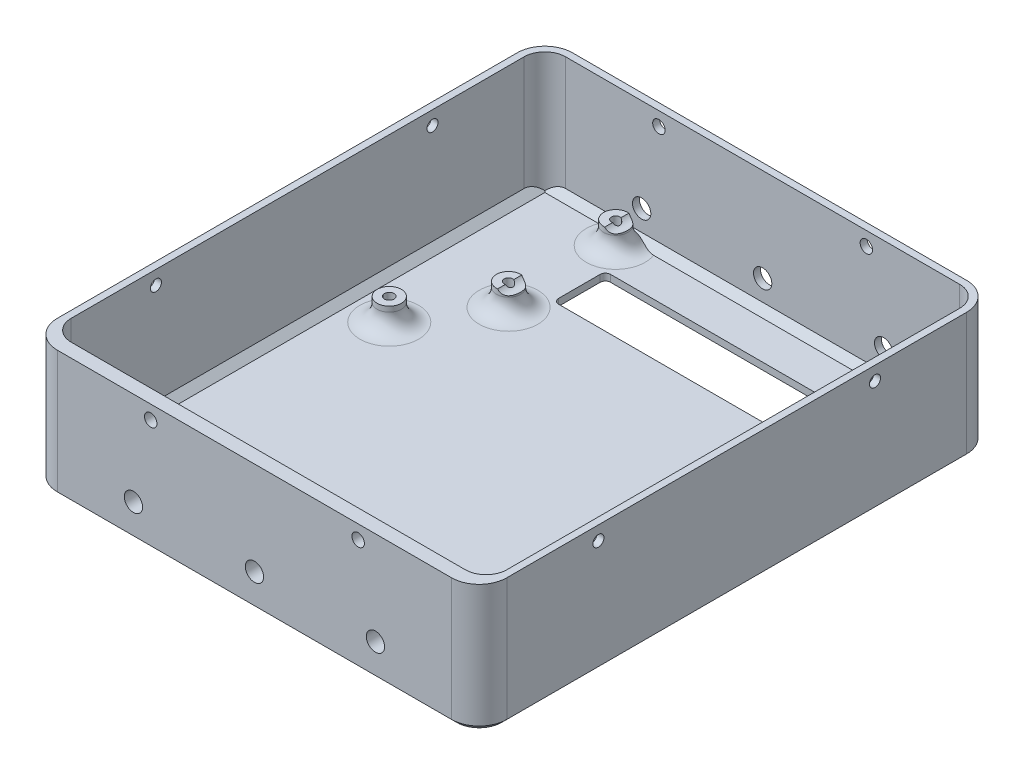
SolidWorks part; units mm, degrees
ref_plane "Front Plane" through (0, 0, 0) normal (0, 0, 1) x (1, 0, 0)
ref_plane "Top Plane" through (0, 0, 0) normal (0, 1, 0) x (1, 0, 0)
ref_plane "Right Plane" through (0, 0, 0) normal (1, 0, 0) x (0, 0, -1)
sketch "Sketch1" plane through (0, 0, 0) normal (0, 1, 0) x (1, 0, 0)
  line L0 (-65, 52) -> (65, 52) construction
  line L1 (-55, -42) -> (55, -42) construction
  line L2 (-55, -42) -> (-55, 42) construction
  line L3 (-55, 42) -> (55, 42) construction
  line L4 (55, -42) -> (55, 42) construction
  line L5 (-55, -42) -> (55, 42) construction
  line L6 (-55, 42) -> (55, -42) construction
  line L7 (51, -38) -> (-51, -38) construction
  line L8 (51, -38) -> (51, 38) construction
  line L9 (51, 38) -> (-51, 38) construction
  line L10 (-51, -38) -> (-51, 38) construction
  line L11 (51, -38) -> (-51, 38) construction
  line L12 (51, 38) -> (-51, -38) construction
  line L13 (65, -52) -> (65, 52)
  line L14 (-65, -52) -> (65, -52)
  line L15 (-65, -52) -> (-65, 52)
  line L16 (-65, 52) -> (-65, 97)
  line L17 (-65, 97) -> (65, 97)
  line L18 (65, 97) -> (65, 52)
  line L19 (0, 52) -> (0, 97) construction
  line L21 (-32.5, 82) -> (32.5, 82)
  line L22 (-32.5, 82) -> (-32.5, 67)
  line L23 (-32.5, 67) -> (32.5, 67)
  line L24 (32.5, 82) -> (32.5, 67)
  line L25 (-32.5, 82) -> (32.5, 67) construction
  line L26 (-32.5, 67) -> (32.5, 82) construction
  line L27 (-37.5, 59) -> (37.5, 59) construction
  line L28 (-37.5, 59) -> (-37.5, 90) construction
  line L29 (-37.5, 90) -> (37.5, 90) construction
  line L30 (37.5, 59) -> (37.5, 90) construction
  line L31 (-37.5, 59) -> (37.5, 90) construction
  line L32 (-37.5, 90) -> (37.5, 59) construction
  circle A0 centre (-51, 38) radius 1.4
  circle A1 centre (51, 38) radius 1.4
  circle A2 centre (51, -38) radius 1.4
  circle A3 centre (-51, -38) radius 1.4
  circle A4 centre (-37.5, 90) radius 1.25
  circle A5 centre (37.5, 90) radius 1.25
  circle A6 centre (37.5, 59) radius 1.25
  circle A7 centre (-37.5, 59) radius 1.25
  point P0 (0, 0)
  point P5 (0, 0)
  point P23 (0, 74.5)
  point P28 (0, 74.5)
  dimension "D1" = 110
  dimension "D5" = 2.8
  dimension "D6" = 2.8
  dimension "D7" = 2.8
  dimension "D8" = 2.8
  dimension "D17" = 2.5
  dimension "D2" = 84
  dimension "D3" = 102
  dimension "D4" = 76
  dimension "D10" = 45
  dimension "D11" = 90
  dimension "D12" = 90
  dimension "D13" = 65
  dimension "D14" = 15
  dimension "D15" = 75
  dimension "D16" = 31
  dimension "D9" = 10
extrude "Boss-Extrude1" add sketch "Sketch1" along normal blind 2
sketch "Sketch2" plane through (0, 2, 0) normal (0, 1, 0) x (1, 0, 0)
  line L0 (-63, 95) -> (-63, -48)
  line L1 (-65, 97) -> (65, 97)
  line L2 (-65, 97) -> (-65, -52)
  line L3 (-65, -52) -> (65, -52)
  line L4 (65, 97) -> (65, -52)
  line L6 (63, 95) -> (63, -48)
  line L7 (-63, 95) -> (63, 95)
  line L8 (-63, 95) -> (-63, -50) construction
  line L11 (-63, -48) -> (63, -48)
  line L13 (-63, -50) -> (63, -50) construction
  line L14 (63, 95) -> (63, -50) construction
  dimension "D1" = 2
  dimension "D2" = 4
extrude "Boss-Extrude2" add sketch "Sketch2" along normal blind 35
sketch "Sketch3" plane through (0, 2, 0) normal (0, 1, 0) x (1, 0, 0)
  circle A0 centre (-51, 38) radius 3.5
  circle A1 centre (-51, 38) radius 1.4
  circle A2 centre (51, 38) radius 1.4
  circle A3 centre (51, 38) radius 3.5
  circle A4 centre (51, -38) radius 1.4764
  circle A5 centre (51, -38) radius 3.5
  circle A6 centre (-51, -38) radius 1.4
  circle A7 centre (-51, -38) radius 3.5
  circle A8 centre (-37.5, 90) radius 1.25
  circle A9 centre (-37.5, 90) radius 3.5
  circle A10 centre (37.5, 90) radius 1.4
  circle A11 centre (37.5, 90) radius 3.5
  circle A12 centre (37.5, 59) radius 1.75
  circle A13 centre (37.5, 59) radius 3.5
  circle A14 centre (-37.5, 59) radius 1.25
  circle A15 centre (-37.5, 59) radius 3.5
  dimension "D1" = 7
  dimension "D2" = 7
  dimension "D3" = 7
  dimension "D4" = 7
extrude "Boss-Extrude3" add sketch "Sketch3" along normal blind 6.5
chamfer "Chamfer1" distance 2 angle 45 4 edges at (63, 2, -23.5) (0, 2, 48) (-63, 2, -23.5) (0, 2, -95)
fillet "Fillet1" radius 5 8 edges at (-51, 2, 34.5) (-51, 2, -41.5) (51, 2, 34.5) (51, 2, -41.5) (-37.5, 2, -62.5) (-37.5, 2, -86.5) (37.5, 2, -62.5) (37.5, 2, -86.5)
fillet "Fillet2" radius 6 4 edges at (63, 20.5, -95) (63, 20.5, 48) (-63, 20.5, 48) (-63, 20.5, -95)
fillet "Fillet3" radius 8 4 edges at (65, 18.5, -97) (-65, 18.5, -97) (65, 18.5, 52) (-65, 18.5, 52)
fillet "Fillet4" radius 1.5 4 edges at (-32.5, 1, -67) (-32.5, 1, -82) (32.5, 1, -82) (32.5, 1, -67)
chamfer "Chamfer2" distance 1.5 angle 45 8 edges at (65, 0, -22.5) (62.6569, 0, -94.6569) (62.6569, 0, 49.6569) (0, 0, -97) (0, 0, 52) (-62.6569, 0, -94.6569) (-62.6569, 0, 49.6569) (-65, 0, -22.5)
sketch "Sketch5" plane through (-65, 0, 0) normal (-1, 0, 0) x (0, 0, 1)
  line L0 (-22.5, 37) -> (-22.5, 33) construction
  line L1 (-89, 37) -> (44, 37) construction
  line L2 (-22.5, 33) -> (-62.5, 33) construction
  circle A0 centre (-62.5, 33) radius 1.6
  circle A1 centre (17.5, 33) radius 1.6
  dimension "D1" = 4
  dimension "D2" = 40
extrude "Cut-Extrude1" cut sketch "Sketch5" against normal up to surface (130 mm away) up to face at (65, 19.25, -22.5)
sketch "Sketch6" plane through (0, 0, -97) normal (0, 0, -1) x (-1, 0, 0)
  line L0 (0, 37) -> (0, 33) construction
  line L1 (-57, 37) -> (57, 37) construction
  line L2 (30, 33) -> (-30, 33) construction
  circle A0 centre (-30, 33) radius 1.8
  circle A1 centre (30, 33) radius 1.8
  point P7 (0, 33)
  dimension "D1" = 4
  dimension "D2" = 60
extrude "Cut-Extrude2" cut sketch "Sketch6" against normal blind 161.5
sketch "Sketch7" plane through (0, 0, 52) normal (0, 0, 1) x (1, 0, 0)
  line L0 (0, 0) -> (0, 20) construction
  line L1 (0, 10) -> (-35, 10) construction
  circle A0 centre (-35, 10) radius 2.65
  circle A1 centre (0, 10) radius 2.65
  circle A2 centre (35, 10) radius 2.65
  dimension "D3" = 3
  dimension "D1" = 20
  dimension "D2" = 35
extrude "Cut-Extrude3" cut sketch "Sketch7" against normal blind 161.5
sketch "Sketch8" plane through (0, 37, 0) normal (0, 1, 0) x (1, 0, 0)
  line L0 (0, 97) -> (0, -52) construction
  line L1 (57, 97) -> (-57, 97) construction
  line L2 (-57, -52) -> (57, -52) construction
  line L3 (0, -52) -> (65, -52) construction
  line L5 (-63, 89) -> (63, 89)
  line L6 (-63, 89) -> (-63, -42)
  line L7 (-63, -42) -> (63, -42)
  line L8 (63, 89) -> (63, -42)
  dimension "D1" = 65
  dimension "D2" = 131
  dimension "D3" = 126
